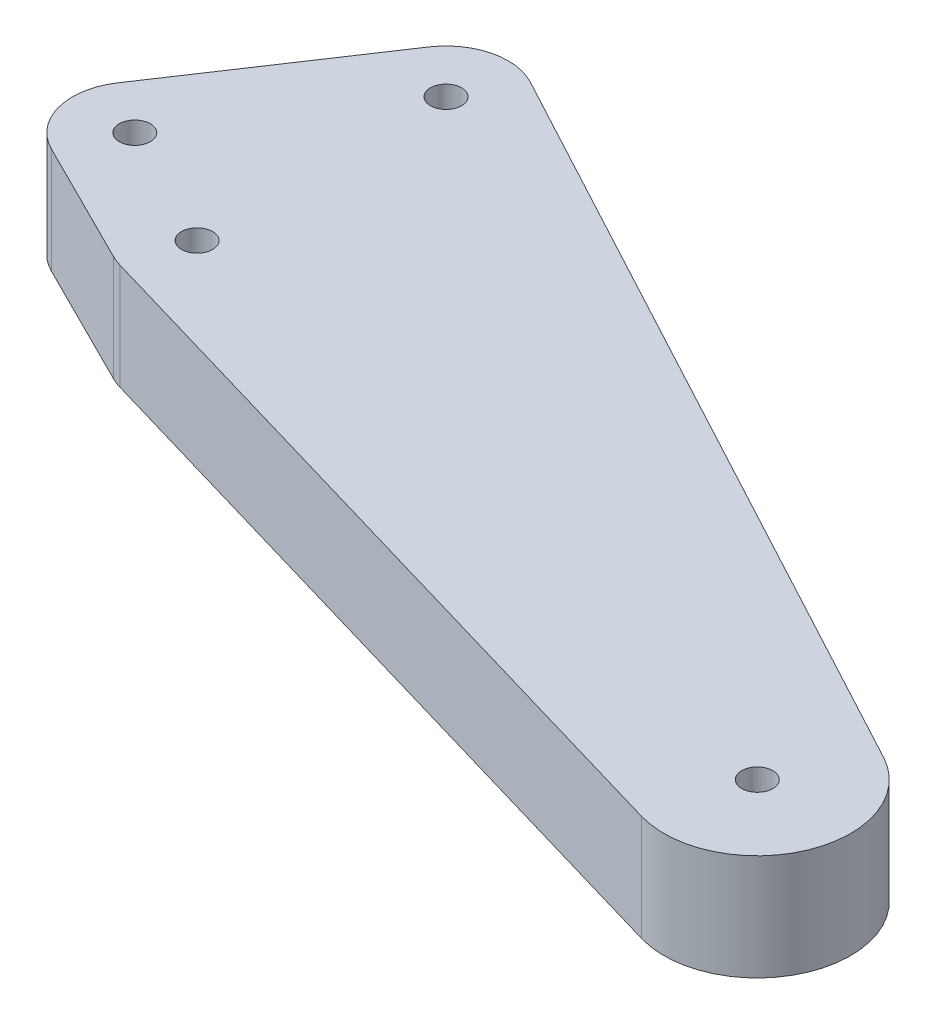
SolidWorks part; units mm, degrees
ref_plane "Front Plane" through (0, 0, 0) normal (0, 0, 1) x (1, 0, 0)
ref_plane "Top Plane" through (0, 0, 0) normal (0, 1, 0) x (1, 0, 0)
ref_plane "Right Plane" through (0, 0, 0) normal (1, 0, 0) x (0, 0, -1)
sketch "Sketch1" plane through (0, 0, 0) normal (0, 1, 0) x (1, 0, 0)
  line L1 (4.7246, 48.8135) -> (127.0868, -16.7797)
  line L2 (115.7767, -44.3932) -> (-2.8155, -9.5955)
  line L4 (-8.3205, 45.547) -> (-28.3205, 15.547)
  line L5 (-24.4721, 1.0557) -> (-4.4721, -8.9443)
  arc A0 (-8.3205, 45.547) -> (4.7246, 48.8135) centre (0, 40) cw
  arc A1 (127.0868, -16.7797) -> (115.7767, -44.3932) centre (120, -30) cw
  arc A2 (-2.8155, -9.5955) -> (-4.4721, -8.9443) centre (0, 0) cw
  arc A3 (-28.3205, 15.547) -> (-24.4721, 1.0557) centre (-20, 10) ccw
  point P11 (-25.3486, 9.6408)
  point P13 (0, 0)
  dimension "D1" = 10
  dimension "D2" = 10
  dimension "D3" = 15
  dimension "D9" = 10
  dimension "D4" = 30
  dimension "D5" = 40
  dimension "D6" = 120
  dimension "D7" = 20
  dimension "D8" = 30
extrude "Boss-Extrude1" add sketch "Sketch1" along normal blind 17
sketch "Sketch2" plane through (0, 17, 0) normal (0, 1, 0) x (1, 0, 0)
  circle A0 centre (0, 40) radius 2.5
  circle A1 centre (0, 0) radius 2.5
  circle A2 centre (120, -30) radius 2.5
  circle A3 centre (-20, 10) radius 2.5
  arc A4 (-28.3205, 15.547) -> (-24.4721, 1.0557) centre (-20, 10) ccw construction
  dimension "D1" = 5
  dimension "D2" = 5
extrude "Cut-Extrude1" cut sketch "Sketch2" against normal through all
